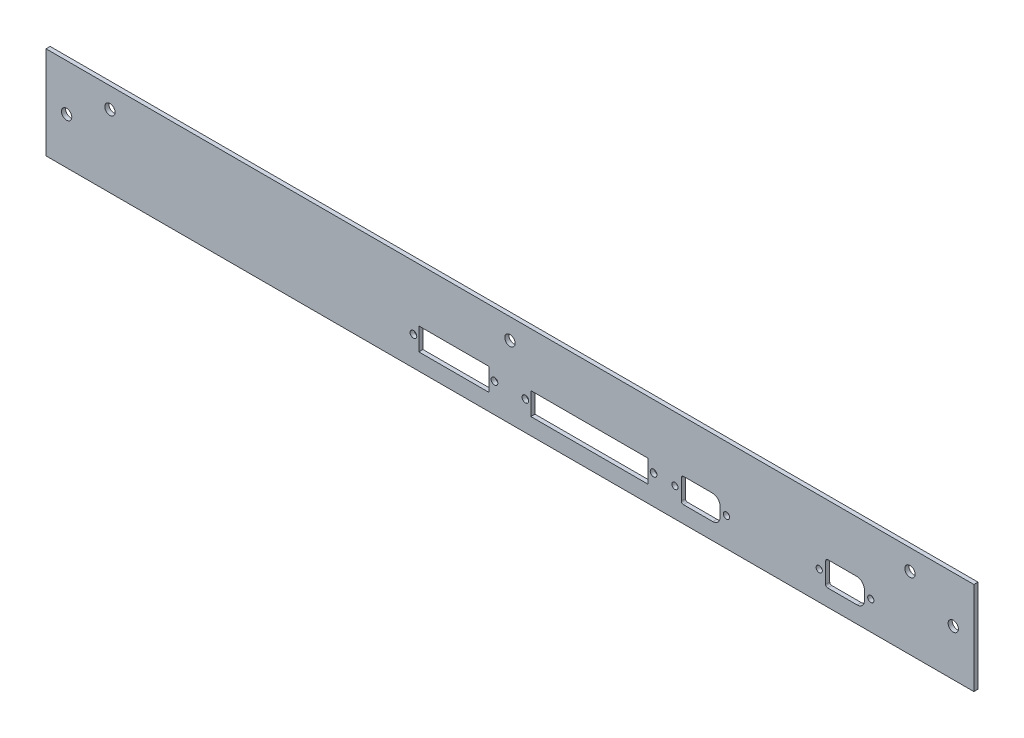
SolidWorks part; units mm, degrees
material "1345 Alloy"
ref_plane "Front Plane" through (0, 0, 0) normal (0, 0, 1) x (1, 0, 0)
ref_plane "Top Plane" through (0, 0, 0) normal (0, 1, 0) x (1, 0, 0)
ref_plane "Right Plane" through (0, 0, 0) normal (1, 0, 0) x (0, 0, -1)
sketch "Sketch1" plane through (0, 0, 0) normal (0, 0, 1) x (1, 0, 0)
  line L1 (-225, 22.5) -> (225, 22.5)
  line L2 (-225, 22.5) -> (-225, -22.5)
  line L3 (-225, -22.5) -> (225, -22.5)
  line L4 (225, 22.5) -> (225, -22.5)
  line L5 (-225, 22.5) -> (225, -22.5) construction
  line L6 (-225, -22.5) -> (225, 22.5) construction
  point P0 (0, 0)
  dimension "D1" = 450
  dimension "D2" = 45
extrude "Boss-Extrude1" add sketch "Sketch1" along normal blind 2
sketch "SK Terminal 12P cutout" plane through (0, 0, 0) normal (0, 0, 1) x (1, 0, 0)
  line L0 (10.125, -14.4) -> (67.045, -14.4)
  line L1 (67.045, -14.4) -> (67.045, -3.5)
  line L2 (67.045, -3.5) -> (10.125, -3.5)
  line L3 (10.125, -3.5) -> (10.125, -14.4)
  line L4 (69.67, 22.5) -> (69.67, -8.35) construction
  line L5 (225, 22.5) -> (-225, 22.5) construction
  line L6 (-7.5, -8.35) -> (-31.415, -8.35) construction
  line L7 (-44.185, -14.4) -> (-10.125, -14.4)
  line L8 (-10.125, -14.4) -> (-10.125, -3.5)
  line L9 (-10.125, -3.5) -> (-44.185, -3.5)
  line L10 (-44.185, -3.5) -> (-44.185, -14.4)
  line L11 (7.5, -8.35) -> (69.67, -8.35) construction
  line L12 (7.5, -8.35) -> (-7.5, -8.35) construction
  line L14 (-31.415, -8.35) -> (-31.415, -3.5) construction
  circle A0 centre (7.5, -8.35) radius 1.625
  circle A1 centre (69.67, -8.35) radius 1.625
  circle A2 centre (-46.81, -8.35) radius 1.625
  circle A3 centre (-7.5, -8.35) radius 1.625
  dimension "D1" = 62.17
  dimension "D2" = 15
extrude "Terminal 12P cutout" cut sketch "SK Terminal 12P cutout" against normal through all and the other way through all
sketch "Sketch2" plane through (0, 0, 2) normal (0, 0, 1) x (1, 0, 0)
  line L0 (-225, 22.5) -> (-215, 22.5) construction
  line L1 (-215, 22.5) -> (-215, 0) construction
  line L2 (-194, 12.4954) -> (194, 12.4954) construction
  line L3 (0, 22.5) -> (0, 12.5) construction
  circle A0 centre (-215, 0) radius 2.5
  circle A1 centre (215, 0) radius 2.5
  circle A2 centre (-194, 12.4954) radius 2.5
  circle A3 centre (194, 12.4954) radius 2.5
  circle A4 centre (0, 12.5) radius 2.5
  dimension "D3" = 5
  dimension "D4" = 5
  dimension "D5" = 5
  dimension "D7" = 5
  dimension "D8" = 5
  dimension "D1" = 10
  dimension "D2" = 22.5
  dimension "D6" = 10
extrude "Cut-Extrude1" cut sketch "Sketch2" against normal through all
sketch "Sketch3" plane through (0, 0, 2) normal (0, 0, 1) x (1, 0, 0)
  line L0 (175, -8.55) -> (225, -8.55) construction
  line L5 (168.375, -14.4) -> (154.1, -14.4)
  line L6 (154.3, -2.5) -> (168.175, -2.5)
  line L7 (153.1, -13.4) -> (153.1, -3.7)
  line L8 (171.9, -10.875) -> (171.9, -6.225)
  line L13 (171.9, -8.55) -> (175, -8.55) construction
  line L15 (225, -22.5) -> (225, 22.5) construction
  line L16 (150, -8.55) -> (153.1, -8.55) construction
  line L17 (98.375, -14.4) -> (84.1, -14.4)
  line L18 (150, -8.55) -> (153.1, -8.55) construction
  line L19 (84.3, -2.5) -> (98.175, -2.5)
  line L20 (83.1, -13.4) -> (83.1, -3.7)
  line L21 (101.9, -10.875) -> (101.9, -6.225)
  line L22 (101.9, -8.55) -> (105, -8.55) construction
  line L23 (80, -8.55) -> (83.1, -8.55) construction
  line L24 (80, -8.55) -> (83.1, -8.55) construction
  line L25 (150, -8.55) -> (105, -8.55) construction
  arc A4 (171.9, -10.875) -> (168.375, -14.4) centre (168.375, -10.875) cw
  arc A5 (171.9, -6.225) -> (168.175, -2.5) centre (168.175, -6.225) ccw
  arc A6 (154.1, -14.4) -> (153.1, -13.4) centre (154.1, -13.4) cw
  arc A7 (153.1, -3.7) -> (154.3, -2.5) centre (154.3, -3.7) cw
  circle A14 centre (150, -8.55) radius 1.5
  circle A15 centre (175, -8.55) radius 1.5
  arc A16 (101.9, -10.875) -> (98.375, -14.4) centre (98.375, -10.875) cw
  arc A17 (101.9, -6.225) -> (98.175, -2.5) centre (98.175, -6.225) ccw
  arc A18 (84.1, -14.4) -> (83.1, -13.4) centre (84.1, -13.4) cw
  arc A19 (83.1, -3.7) -> (84.3, -2.5) centre (84.3, -3.7) cw
  circle A20 centre (80, -8.55) radius 1.5
  circle A21 centre (105, -8.55) radius 1.5
  dimension "D3" = 3
  dimension "D4" = 3
  dimension "D5" = 3
  dimension "D6" = 3
  dimension "D7" = 25
  dimension "D2" = 50
  dimension "D8" = 5.85
  dimension "D9" = 45
  dimension "D10" = 25
  dimension "D13" = 5.85
extrude "Cut-Extrude2" cut sketch "Sketch3" against normal blind 10
